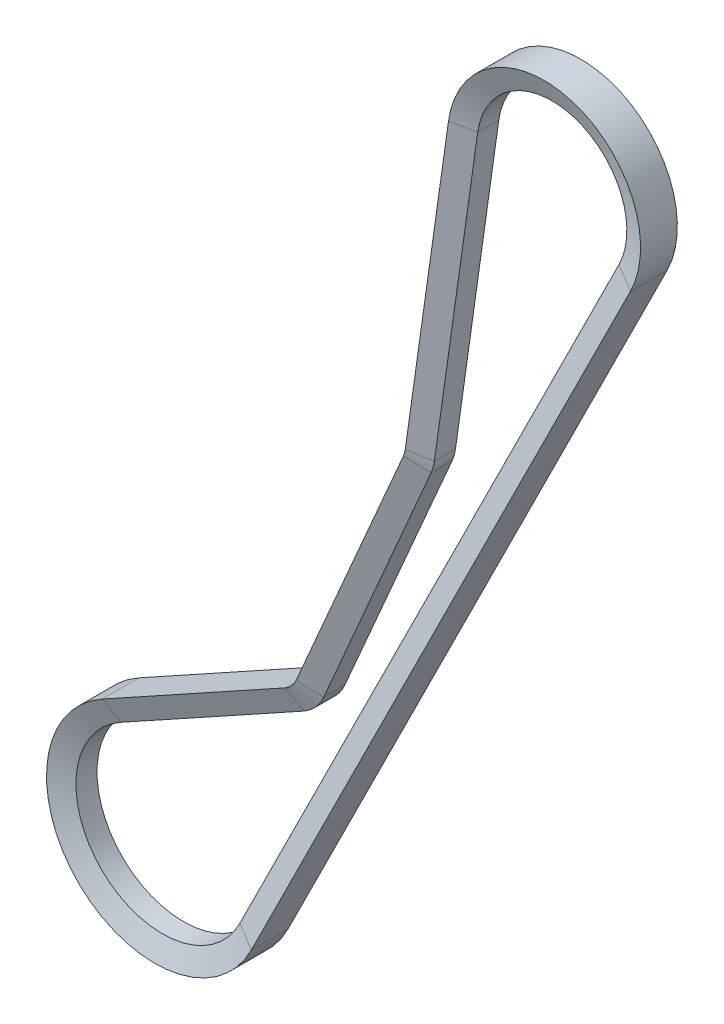
SolidWorks part; units mm, degrees
ref_plane "Front Plane" through (0, 0, 0) normal (0, 0, 1) x (1, 0, 0)
ref_plane "Top Plane" through (0, 0, 0) normal (0, 1, 0) x (1, 0, 0)
ref_plane "Right Plane" through (0, 0, 0) normal (1, 0, 0) x (0, 0, -1)
sketch "Sketch2" plane through (0, 0, 0) normal (0, 0, 1) x (1, 0, 0)
  line L0 (0, 0) -> (1, 0) construction
  line L1 (0, 0) -> (0, 1) construction
  line L12 (22.3711, -11.1594) -> (-75.8226, -208.007)
  line L14 (-114.4306, -171.0068) -> (-66.9899, -144.7665)
  line L15 (-64.2359, -141.7323) -> (-36.4297, -77.4919)
  line L16 (-35.9697, -75.8582) -> (-24.754, 3.4986)
  arc A4 (-75.8226, -208.007) -> (-114.4306, -171.0068) centre (-100.8783, -195.5085) cw
  arc A7 (-24.754, 3.4986) -> (22.3711, -11.1594) centre (0, 0) cw
  arc A8 (-66.9899, -144.7665) -> (-64.2359, -141.7323) centre (-70.0634, -139.2098) ccw
  arc A9 (-36.4297, -77.4919) -> (-35.9697, -75.8582) centre (-42.2572, -74.9695) ccw
ref_plane "Plane4" through (-24.754, 3.4986, 0) normal (0.1399, 0.9902, 0) x (0.9902, -0.1399, 0)
sketch "Sketch3" plane through (-24.754, 3.4986, 0) normal (0.1399, 0.9902, 0) x (0.9902, -0.1399, 0)
  line L0 (0, -4.7625) -> (0, 4.7625)
  line L1 (0, -4.7625) -> (5.588, -2.7286)
  line L2 (5.588, -2.7286) -> (5.588, 2.7286)
  line L3 (5.588, 2.7286) -> (0, 4.7625)
  line L4 (0, 0) -> (5.588, 0) construction
  dimension "D1" = 9.525
  dimension "D2" = 5.588
  dimension "D3" = 40
sweep "Sweep1" add profiles "Sketch3" path "Sketch2"
